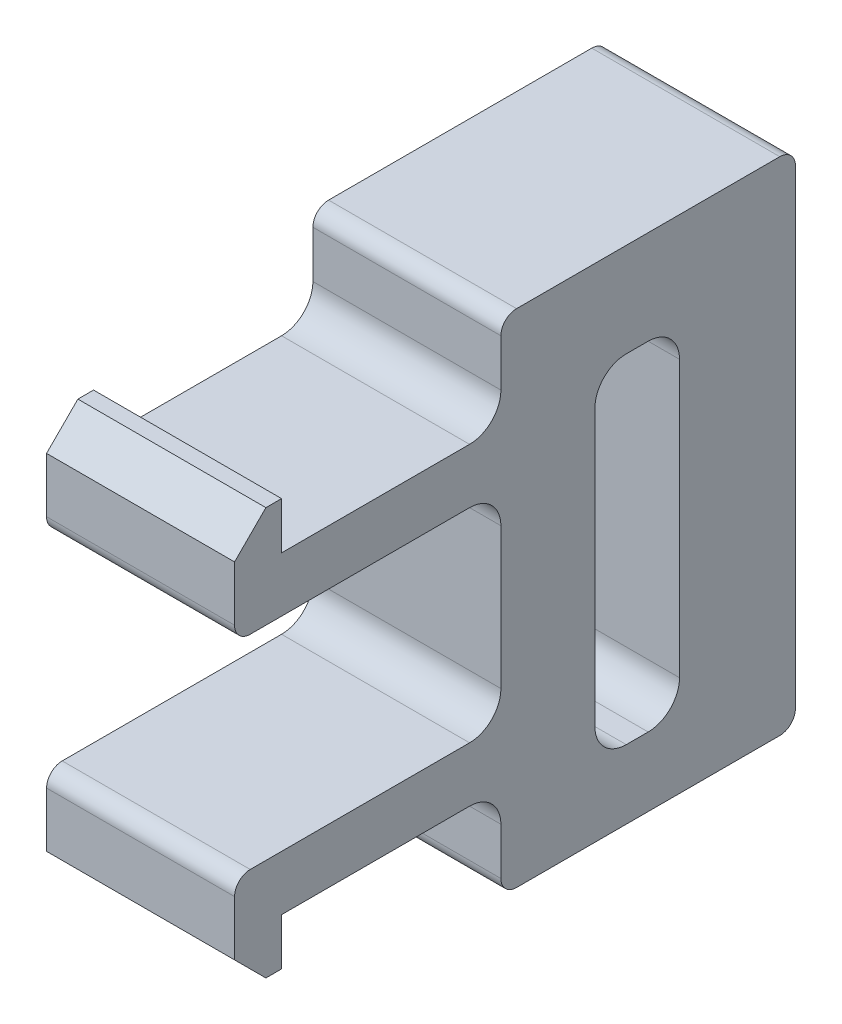
SolidWorks part; units mm, degrees
material "ABS"
ref_plane "Plan de face" through (0, 0, 0) normal (0, 0, 1) x (1, 0, 0)
ref_plane "Plan de dessus" through (0, 0, 0) normal (0, 1, 0) x (1, 0, 0)
ref_plane "Plan de droite" through (0, 0, 0) normal (1, 0, 0) x (0, 0, -1)
sketch "Esquisse1" plane through (0, 0, 0) normal (0, 0, 1) x (1, 0, 0)
  line L0 (52.8, 45.5898) -> (52.8, 29.5898)
  line L3 (52.8, 29.5898) -> (58.8, 29.5898)
  line L4 (58.8, 29.5898) -> (58.8, 45.5898)
  line L5 (58.8, 45.5898) -> (52.8, 45.5898)
  line L6 (55.8, 42.4523) -> (55.8, 32.7471) construction
  dimension "D1" = 6
  dimension "D2" = 16
extrude "Extrusion1" add sketch "Esquisse1" along normal blind 3.7
sketch "Esquisse2" plane through (0, 0, 3.7) normal (0, 0, 1) x (1, 0, 0)
  line L0 (52.8, 45.5898) -> (52.8, 42.5898)
  line L1 (52.8, 45.5898) -> (58.8, 45.5898)
  line L2 (52.8, 42.5898) -> (58.8, 42.5898)
  line L3 (58.8, 45.5898) -> (58.8, 42.5898)
  line L4 (52.8, 45.5898) -> (52.8, 29.5898) construction
  line L5 (58.8, 29.5898) -> (58.8, 45.5898) construction
  line L6 (55.8, 29.5898) -> (55.8, 31.7898)
  line L7 (55.8, 29.5898) -> (58.8, 29.5898)
  line L8 (55.8, 31.7898) -> (58.8, 31.7898)
  line L9 (58.8, 29.5898) -> (58.8, 31.7898)
  dimension "D1" = 3
  dimension "D2" = 2.2
  dimension "D3" = 3
extrude "Extrusion2" add sketch "Esquisse2" along normal blind 2.7
sketch "Esquisse3" plane through (0, 0, 3.7) normal (0, 0, 1) x (1, 0, 0)
  line L0 (52.8, 29.5898) -> (55.8, 29.5898)
  line L1 (52.8, 29.5898) -> (52.8, 40.5898)
  line L2 (55.8, 29.5898) -> (55.8, 40.5898)
  line L3 (52.8, 40.5898) -> (55.8, 40.5898)
  line L4 (52.8, 29.5898) -> (55.8, 29.5898) construction
  line L5 (55.8, 31.7898) -> (55.8, 29.5898) construction
  dimension "D1" = 11
extrude "Enlèv. mat.-Extru.1" cut sketch "Esquisse3" against normal blind 5
sketch "Esquisse4" plane through (0, 0, 6.4) normal (0, 0, 1) x (1, 0, 0)
  line L0 (52.8, 45.5898) -> (52.8, 29.5898)
  line L1 (52.8, 45.5898) -> (58.8, 45.5898)
  line L2 (58.8, 45.5898) -> (58.8, 29.5898)
  line L3 (58.8, 29.5898) -> (52.8, 29.5898)
extrude "Extrusion3" add sketch "Esquisse4" along normal blind 3
sketch "Esquisse5" plane through (52.8, 0, 0) normal (-1, 0, 0) x (0, 0, 1)
  line L0 (9.4, 37.5898) -> (12.3106, 37.5898) construction
  line L1 (9.4, 45.5898) -> (9.4, 29.5898) construction
  line L2 (8.1832, 42.5898) -> (16.4, 42.5898)
  line L4 (17.9, 44.0898) -> (17.9, 40.8398)
  line L5 (8.1832, 32.5898) -> (16.4, 32.5898)
  line L6 (16.4, 42.5898) -> (16.4, 44.0898)
  line L7 (16.4, 44.0898) -> (17.9, 44.0898)
  line L8 (16.4, 32.5898) -> (16.4, 31.0898)
  line L9 (16.4, 31.0898) -> (17.9, 31.0898)
  line L10 (17.9, 40.8398) -> (9.2, 40.8398)
  line L11 (8.1832, 42.5898) -> (8.1832, 32.5898)
  line L12 (9.2, 40.8398) -> (9.2, 34.3398)
  line L13 (17.9, 34.3398) -> (9.2, 34.3398)
  line L15 (17.9, 34.3398) -> (17.9, 31.0898)
  dimension "D1" = 10
  dimension "D2" = 1.5
  dimension "D3" = 1.5
  dimension "D4" = 6.5
  dimension "D5" = 8.5
  dimension "D6" = 8.7
  dimension "D7" = 1.5
extrude "Extrusion4" add sketch "Esquisse5" along direction (-1, 0, 0) on the side against the normal up to surface (6 mm away) up to face at (58.8, 37.5898, 4.7)
chamfer "Chanfrein1" distance 1 angle 45 2 edges at (55.8, 31.0898, 17.9) (55.8, 44.0898, 17.9)
fillet "Congé1" radius 1 9 edges at (55.8, 40.5898, 1.85) (55.8, 42.5898, 6.4) (57.3, 31.7898, 3.7) (57.3, 31.7898, 6.4) (55.8, 34.3398, 9.4) (55.8, 42.5898, 9.4) (55.8, 32.5898, 9.4) (55.8, 40.8398, 9.4)
fillet "Congé2" radius 0.5 6 edges at (55.8, 34.3398, 17.9) (55.8, 40.8398, 17.9) (55.8, 45.5898, 9.4) (55.8, 45.5898, 0) (55.8, 29.5898, 9.4) (57.3, 29.5898, 0)
sketch "Esquisse6" plane through (0, 0, 0) normal (0, 0, -1) x (-1, 0, 0)
  line L0 (-56.8, 29.5898) -> (-52.3818, 46.0786)
  line L1 (-55.8, 29.5898) -> (-58.8, 29.5898) construction
  line L2 (-58.8, 30.0898) -> (-58.8, 45.0898) construction
  line L3 (-52.8, 29.5898) -> (-55.8, 29.5898) construction
  line L4 (-56.8, 29.5898) -> (-52.3818, 29.5898)
  line L5 (-52.3818, 29.5898) -> (-52.3818, 46.0786)
  dimension "D1" = 2
  dimension "D2" = 75
extrude "Enlèv. mat.-Extru.2" cut sketch "Esquisse6" against normal up to surface (6.4 mm away) up to face at (55.8, 34.6564, 6.4)
